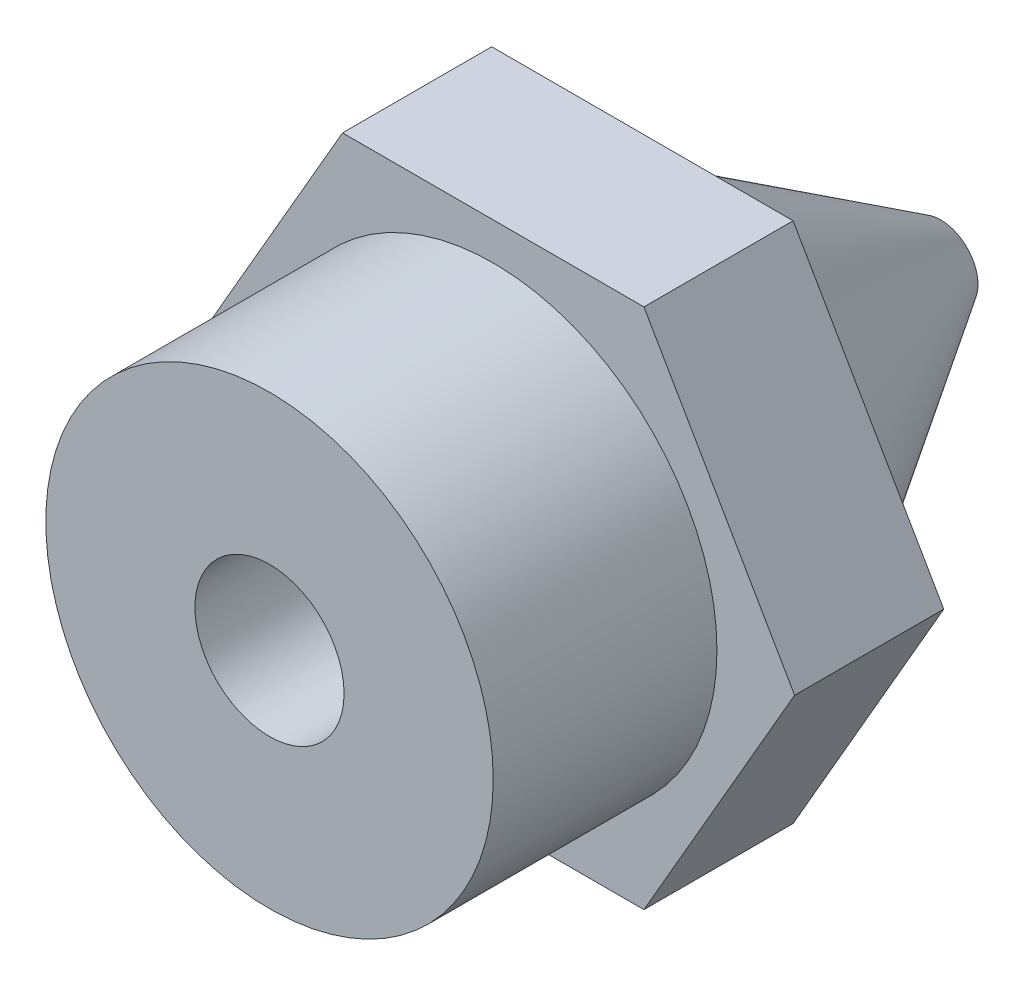
SolidWorks part; units mm, degrees
ref_plane "Plan de face" through (0, 0, 0) normal (0, 0, 1) x (1, 0, 0)
ref_plane "Plan de dessus" through (0, 0, 0) normal (0, 1, 0) x (1, 0, 0)
ref_plane "Plan de droite" through (0, 0, 0) normal (1, 0, 0) x (0, 0, -1)
sketch "Esquisse1" plane through (0, 0, 0) normal (0, 0, 1) x (1, 0, 0)
  line L1 (4.0415, 0) -> (2.0207, 3.5)
  line L2 (2.0207, 3.5) -> (-2.0207, 3.5)
  line L3 (-2.0207, 3.5) -> (-4.0415, 0)
  line L4 (-4.0415, 0) -> (-2.0207, -3.5)
  line L5 (-2.0207, -3.5) -> (2.0207, -3.5)
  line L6 (2.0207, -3.5) -> (4.0415, 0)
  circle A0 centre (0, 0) radius 3.5 construction
  dimension "D1" = 7
extrude "Boss.-Extru.1" add sketch "Esquisse1" along normal blind 9
sketch "Esquisse2" plane through (0, 0, 9) normal (0, 0, 1) x (1, 0, 0)
  line L1 (-7.9912, 5.5023) -> (7.566, 5.5023)
  line L2 (-7.9912, 5.5023) -> (-7.9912, -5.9665)
  line L3 (-7.9912, -5.9665) -> (7.566, -5.9665)
  line L4 (7.566, 5.5023) -> (7.566, -5.9665)
  circle A0 centre (0, 0) radius 3
  dimension "D1" = 6
extrude "Enlèv. mat.-Extru.1" cut sketch "Esquisse2" against normal blind 3
cosmetic thread "Représentation de filetage1" parameters "D2"=4.891
hole_wizard "Diamètre du perçage Ø2.0 (2)1" positions "Esquisse5" profile "Esquisse6" hole size "Ø2.0" standard "ISO"
sketch "Esquisse5" plane through (0, 0, 9) normal (0, 0, 1) x (1, 0, 0)
  point P0 (0, 0)
sketch "Esquisse6" plane through (0, 0, 9) normal (1, 0, 0) x (0, -1, 0)
  line L0 (0, 0) -> (0, 8.1009)
  line L1 (0, 8.1009) -> (1, 7.5)
  line L2 (1, 7.5) -> (1, 0)
  line L5 (1, 0) -> (0, 0)
  line L10 (0, 8.1009) -> (-1, 7.5) construction
  line L11 (0, -6.35) -> (0, 107.95) construction
  dimension "Diamètre du perçage" = 2
  dimension "Profondeur du perçage" = 7.5
  dimension "Angle de pointe" = 118
hole_wizard "Diamètre du perçage Ø1.5 (1.5)1" positions "Esquisse8" profile "Esquisse7" hole size "Ø1.5" standard "ISO"
sketch "Esquisse8" plane through (0, 0, 9) normal (0, 0, 1) x (1, 0, 0)
  point P0 (0, 0)
sketch "Esquisse7" plane through (0, 0, 9) normal (1, 0, 0) x (0, -1, 0)
  line L0 (0, 0) -> (0, 8.6506)
  line L1 (0, 8.6506) -> (0.75, 8.2)
  line L2 (0.75, 8.2) -> (0.75, 0)
  line L5 (0.75, 0) -> (0, 0)
  line L10 (0, 8.6506) -> (-0.75, 8.2) construction
  line L11 (0, -6.35) -> (0, 107.95) construction
  dimension "Diamètre du perçage" = 1.5
  dimension "Profondeur du perçage" = 8.2
  dimension "Angle de pointe" = 118
hole_wizard "Diamètre du perçage Ø0.4 (0.4)1" positions "Esquisse10" profile "Esquisse9" hole size "Ø0.4" standard "ISO"
sketch "Esquisse10" plane through (0, 0, 0) normal (0, 0, -1) x (-1, 0, 0)
  point P0 (0, 0)
sketch "Esquisse9" plane through (0, 0, 0) normal (1, 0, 0) x (0, 1, 0)
  line L0 (0, 0) -> (0, 0.8202)
  line L1 (0, 0.8202) -> (0.2, 0.7)
  line L2 (0.2, 0.7) -> (0.2, 0)
  line L5 (0.2, 0) -> (0, 0)
  line L10 (0, 0.8202) -> (-0.2, 0.7) construction
  line L11 (0, -6.35) -> (0, 107.95) construction
  dimension "Diamètre du perçage" = 0.4
  dimension "Profondeur du perçage" = 0.7
  dimension "Angle de pointe" = 118
sketch "Esquisse3" plane through (0, 0, 0) normal (0, 0, -1) x (-1, 0, 0)
  line L1 (7.8656, -6.0768) -> (-7.4574, -6.0768)
  line L2 (7.8656, -6.0768) -> (7.8656, 5.7844)
  line L3 (7.8656, 5.7844) -> (-7.4574, 5.7844)
  line L4 (-7.4574, -6.0768) -> (-7.4574, 5.7844)
  circle A0 centre (0, 0) radius 3
  dimension "D1" = 6
extrude "Enlèv. mat.-Extru.3" cut sketch "Esquisse3" against normal blind 4
chamfer "Chanfrein2" distance 4 angle 32 1 edges at (-3, 0, 0) first distance on face at (-3, 0, 4)
